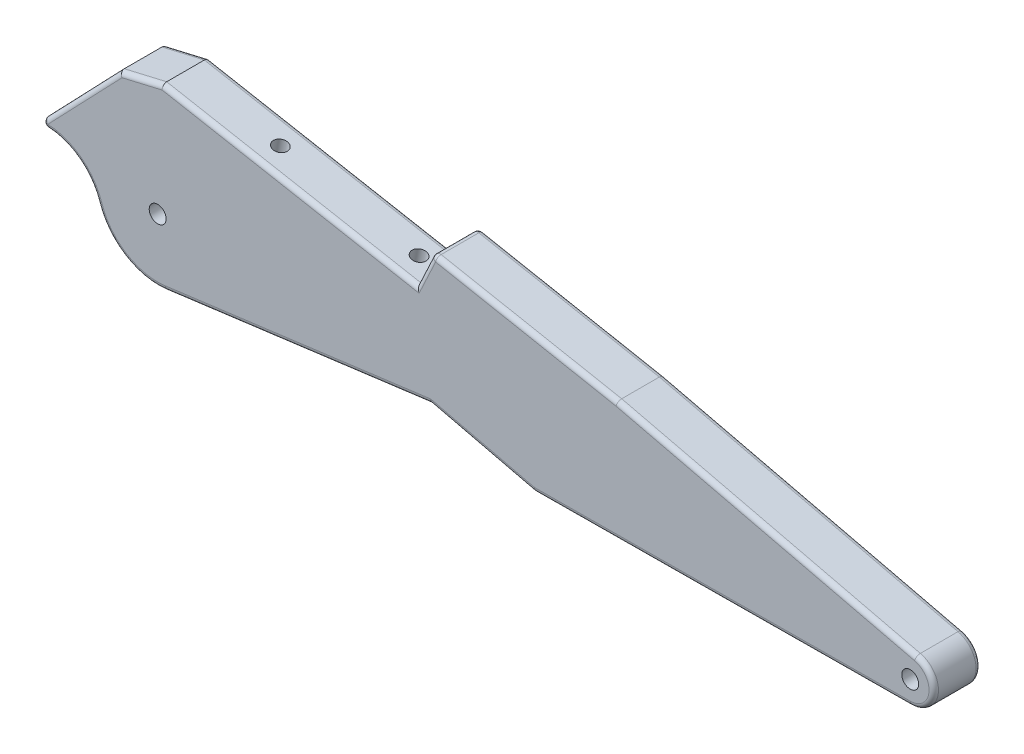
SolidWorks part; units mm, degrees
ref_plane "Front Plane" through (0, 0, 0) normal (0, 0, 1) x (1, 0, 0)
ref_plane "Top Plane" through (0, 0, 0) normal (0, 1, 0) x (1, 0, 0)
ref_plane "Right Plane" through (0, 0, 0) normal (1, 0, 0) x (0, 0, -1)
sketch "Sketch1" plane through (0, 0, 0) normal (0, 0, 1) x (1, 0, 0)
  line L1 (0.0486, -6.3498) -> (-101.5514, -7.1275)
  line L2 (-101.5514, -7.1275) -> (-129.54, -0.456)
  line L6 (-128.905, 34.925) -> (-133.35, 25.4)
  line L7 (-200.977, -9.7973) -> (-129.54, -0.456)
  line L8 (-133.35, 25.4) -> (-202.0358, 38.1)
  line L9 (-202.0358, 38.1) -> (-213.4849, 35.424)
  line L10 (-128.905, 34.925) -> (-79.1726, 25.4)
  line L11 (-79.1726, 25.4) -> (-128.905, 34.925) construction
  line L12 (-79.1726, 25.4) -> (1.4724, 6.1769)
  line L13 (-129.5991, 33.4375) -> (-133.35, 25.4) construction
  line L17 (-133.35, 25.4) -> (-202.0358, 38.1) construction
  line L18 (-17.145, -27.2472) -> (-129.54, -0.456) construction
  line L19 (-200.977, -9.7973) -> (-129.54, -0.456) construction
  line L20 (-107.0451, 30.7383) -> (-127.6185, 34.6786) construction
  line L21 (-177.0742, 43.9341) -> (-213.4849, 35.424) construction
  line L22 (-235.9783, 11.9479) -> (-213.4849, 35.424)
  line L24 (-17.145, -27.2472) -> (-129.54, -0.456) construction
  line L25 (-233.7591, 14.2641) -> (-213.7458, 35.1518) construction
  line L29 (-79.1726, 25.4) -> (1.4724, 6.1769) construction
  line L31 (-129.54, -0.456) -> (-200.977, -9.7973) construction
  circle A0 centre (0, 0) radius 2.286
  arc A1 (0.0486, -6.3498) -> (1.4724, 6.1769) centre (0, 0) ccw
  circle A2 centre (-203.2, 7.203) radius 2.286
  arc A6 (-219.4987, 1.8827) -> (-200.977, -9.7973) centre (-203.2, 7.203) ccw
  circle A7 centre (-203.2, 7.203) radius 4.826 construction
  arc A8 (4.6019, -4.3755) -> (1.4724, 6.1769) centre (0, 0) ccw construction
  arc A9 (-235.9783, 11.9479) -> (-219.4987, 1.8827) centre (-233.6294, -2.7298) cw
  arc A10 (-200.977, -9.7973) -> (-219.4987, 1.8827) centre (-203.2, 7.203) ccw construction
  arc A13 (-219.4987, 1.8827) -> (-232.9041, 12.117) centre (-233.6294, -2.7298) ccw construction
  point P17 (105.4504, -19.602)
  point P18 (-71.2573, 0.0759)
  dimension "D1" = 4.572
  dimension "D2" = 101.6
extrude "Boss-Extrude1" add sketch "Sketch1" along normal blind 12.7
fillet "Fillet1" radius 1.27 26 edges at (-165.2585, -5.1266, 12.7) (-212.3453, -7.2993, 12.7) (-38.8501, 15.7885, 12.7) (-225.8815, 9.9557, 0) (-212.3453, -7.2993, 0) (-50.7514, -6.7387, 0) (-225.8815, 9.9557, 12.7) (-224.7316, 23.686, 12.7) (-207.7603, 36.762, 12.7) (-167.6929, 31.75, 12.7) (-131.1275, 30.1625, 0) (-131.1275, 30.1625, 12.7) (-104.0388, 30.1625, 12.7) (-115.5457, -3.7917, 12.7) (-50.7514, -6.7387, 12.7) (-207.7603, 36.762, 0) (-224.7316, 23.686, 0) (-167.6929, 31.75, 0) (-128.905, 34.925, 6.35) (-165.2585, -5.1266, 0) (-115.5457, -3.7917, 0) (-38.8501, 15.7885, 0) (-104.0388, 30.1625, 0) (6.3094, -0.7171, 12.7) (6.3094, -0.7171, 0) (-235.9783, 11.9479, 6.35)
sketch "Sketch2" plane through (0, 0, 0) normal (0, 0, -1) x (-1, 0, 0)
  circle A0 centre (0, 0) radius 5.2387
  dimension "D1" = 10.4775
extrude "Cut-Extrude1" cut sketch "Sketch2" against normal blind 3.9688
sketch "Sketch3" plane through (0.1329, 0.719, 0) normal (0.1818, 0.9833, 0) x (0.9833, -0.1818, 0)
  circle A0 centre (-179.5561, -6.35) radius 1.905
  circle A1 centre (-141.4561, -6.35) radius 1.905
  dimension "D1" = 3.81
extrude "Cut-Extrude2" cut sketch "Sketch3" against normal blind 12.7
sketch "Sketch4" plane through (-129.0002, 123.6, 0) normal (-0.7221, 0.6918, 0) x (0, 0, 1)
  line L0 (0, -151.4225) -> (0, -122.4945) construction
  line L1 (1.27, -152.6925) -> (11.43, -152.6925) construction
  circle A0 centre (6.35, -146.3425) radius 1.905
  dimension "D1" = 3.81
  dimension "D2" = 6.35
  dimension "D3" = 6.35
extrude "Cut-Extrude3" cut sketch "Sketch4" against normal blind 12.7
